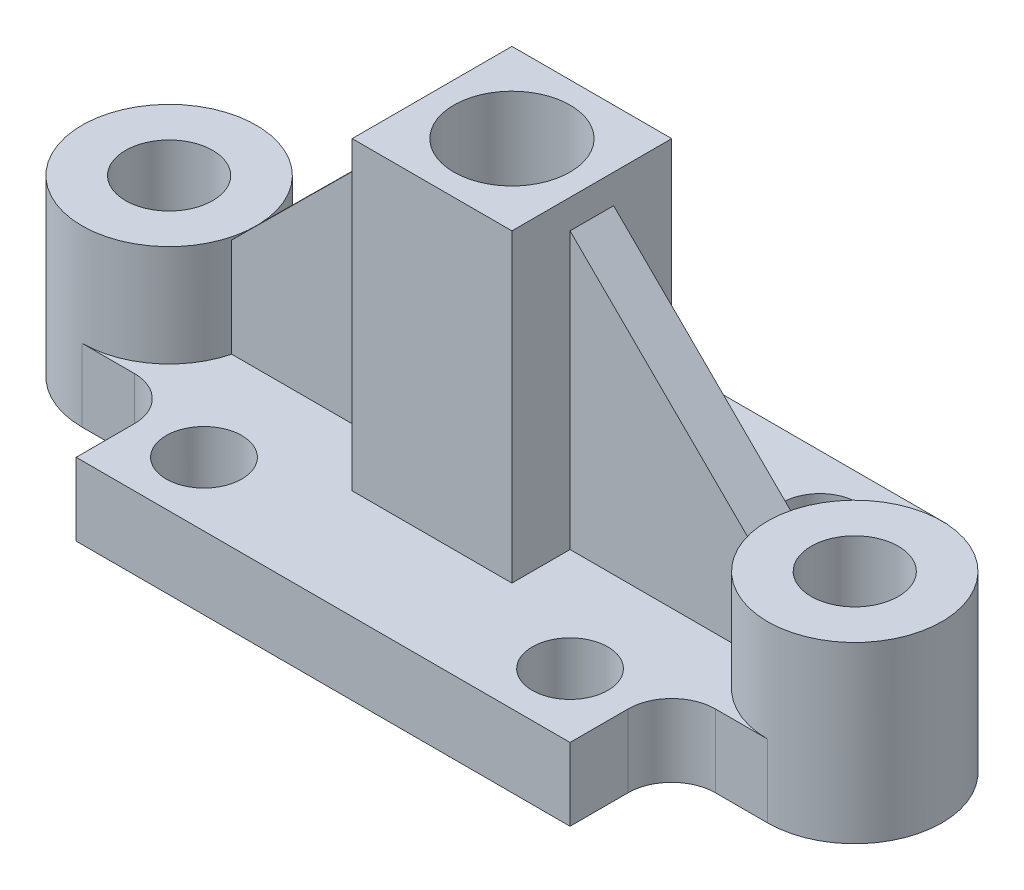
SolidWorks part; units mm, degrees
ref_plane "Front Plane" through (0, 0, 0) normal (0, 0, 1) x (1, 0, 0)
ref_plane "Top Plane" through (0, 0, 0) normal (0, 1, 0) x (1, 0, 0)
ref_plane "Right Plane" through (0, 0, 0) normal (1, 0, 0) x (0, 0, -1)
sketch "Sketch1" plane through (0, 0, 0) normal (0, 1, 0) x (1, 0, 0)
  line L0 (-137.6126, 0) -> (146.982, 0) construction
  line L1 (0, 80.2252) -> (0, -92.3273) construction
  line L2 (118, 30) -> (100, 30)
  line L3 (-85, 65) -> (85, 65)
  line L4 (-85, 45) -> (-85, 65)
  line L5 (85, 45) -> (85, 65)
  line L6 (-118, 30) -> (-100, 30)
  line L7 (-85, -65) -> (85, -65)
  line L8 (118, -30) -> (100, -30)
  line L9 (85, -45) -> (85, -65)
  line L10 (-118, -30) -> (-100, -30)
  line L11 (-85, -45) -> (-85, -65)
  circle A0 centre (118, 0) radius 30
  circle A1 centre (118, 0) radius 15
  circle A2 centre (-118, 0) radius 15
  circle A3 centre (-118, 0) radius 30
  arc A4 (-100, 30) -> (-85, 45) centre (-100, 45) ccw
  arc A5 (100, 30) -> (85, 45) centre (100, 45) cw
  arc A6 (100, -30) -> (85, -45) centre (100, -45) ccw
  arc A7 (-100, -30) -> (-85, -45) centre (-100, -45) cw
  point P10 (0, 65)
  point P32 (0, 0)
  dimension "D3" = 60
  dimension "D5" = 30
  dimension "D6" = 15
  dimension "D1" = 65
  dimension "D2" = 170
  dimension "D4" = 118
  dimension "D7" = 236
extrude "Boss-Extrude1" add sketch "Sketch1" along normal mid plane 25 contours L10 A7 L11 L7 L9 A6 L8 A0 L2 A5 L5 L3 L4 A4 L6 A3 region at (0, 0, 0)
extrude "Boss-Extrude2" add sketch "Sketch1<3>" along normal blind 47.5 and the other way up to surface (12.5 mm away) contours A3 A2 | A0 A1 region at (138.6132, 0, -20.6132) region at (-97.3868, 0, -20.6132) other way up to face at (0, -12.5, 0)
sketch "Sketch1<3>" plane through (0, 0, 0) normal (0, 1, 0) x (1, 0, 0) same geometry as "Sketch1"
sketch "Sketch2" plane through (0, 12.5, 0) normal (0, 1, 0) x (1, 0, 0)
  line L0 (0, 96.325) -> (0, -114.6726) construction
  line L1 (-160.5417, 0) -> (189.9945, 0) construction
  line L2 (-85, 45) -> (-85, 65) construction
  line L3 (-85, 65) -> (85, 65) construction
  circle A0 centre (-63, 43) radius 13
  circle A3 centre (-63, -43) radius 13
  circle A4 centre (63, 43) radius 13
  circle A5 centre (63, -43) radius 13
  dimension "D1" = 26
  dimension "D3" = 22
  dimension "D2" = 22
extrude "Cut-Extrude1" cut sketch "Sketch2" against normal up to next
sketch "Sketch3" plane through (0, 12.5, 0) normal (0, 1, 0) x (1, 0, 0)
  line L1 (-27.5, 27.5) -> (27.5, 27.5)
  line L2 (-27.5, 27.5) -> (-27.5, -27.5)
  line L3 (-27.5, -27.5) -> (27.5, -27.5)
  line L4 (27.5, 27.5) -> (27.5, -27.5)
  line L5 (-27.5, 27.5) -> (27.5, -27.5) construction
  line L6 (-27.5, -27.5) -> (27.5, 27.5) construction
  point P0 (0, 0)
  dimension "D1" = 55
  dimension "D2" = 55
extrude "Boss-Extrude3" add sketch "Sketch3" along normal blind 105
sketch "Sketch4" plane through (0, 117.5, 0) normal (0, 1, 0) x (1, 0, 0)
  circle A0 centre (0, 0) radius 20
  dimension "D1" = 40
extrude "Cut-Extrude2" cut sketch "Sketch4" against normal up to next
sketch "Sketch6" plane through (0, 0, 0) normal (0, 0, 1) x (1, 0, 0)
  line L0 (-89.1689, 12.5) -> (-89.1689, 46.3407)
  line L1 (-89.1689, 12.5) -> (-27.5, 12.5)
  line L2 (-27.5, 12.5) -> (-27.5, 107.5)
  line L3 (-27.5, 117.5) -> (-27.5, 12.5) construction
  line L4 (-27.5, 107.5) -> (-89.1689, 46.3407)
  dimension "D1" = 95
extrude "Boss-Extrude5" add sketch "Sketch6" along normal mid plane 15 separate body
mirror "Mirror6" about plane through (0, 0, 0) normal (1, 0, 0) of bodies 107
